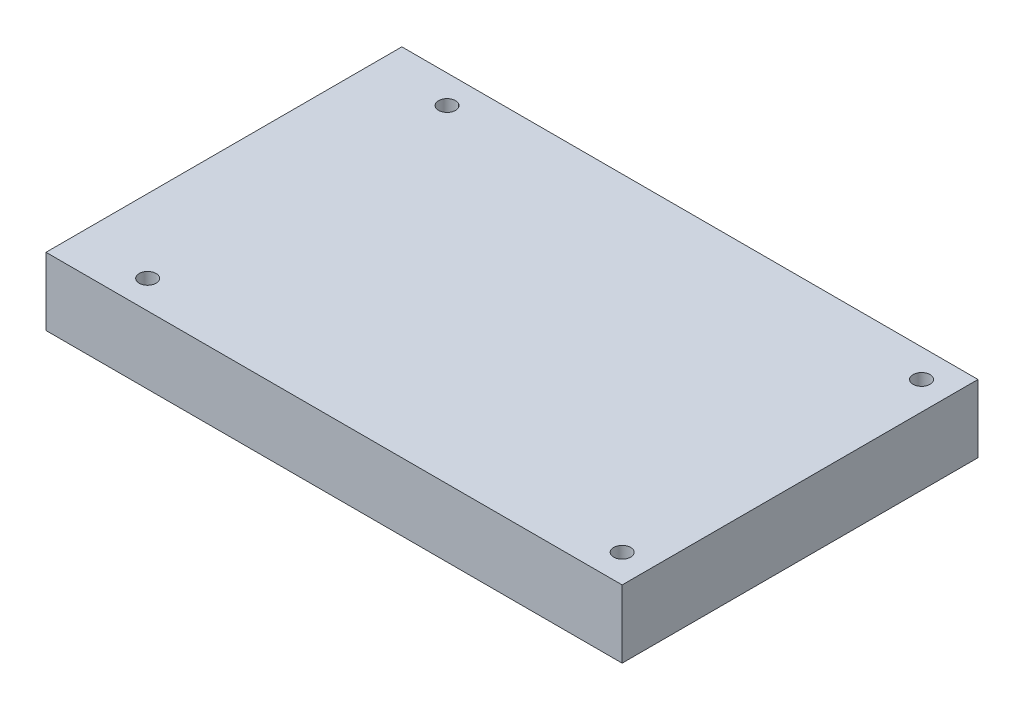
SolidWorks part; units mm, degrees
ref_plane "Front Plane" through (0, 0, 0) normal (0, 0, 1) x (1, 0, 0)
ref_plane "Top Plane" through (0, 0, 0) normal (0, 1, 0) x (1, 0, 0)
ref_plane "Right Plane" through (0, 0, 0) normal (1, 0, 0) x (0, 0, -1)
sketch "Sketch1" plane through (0, 0, 0) normal (0, 1, 0) x (1, 0, 0)
  line L1 (51, -31.5) -> (-51, -31.5)
  line L2 (51, -31.5) -> (51, 31.5)
  line L3 (51, 31.5) -> (-51, 31.5)
  line L4 (-51, -31.5) -> (-51, 31.5)
  line L5 (51, -31.5) -> (-51, 31.5) construction
  line L6 (51, 31.5) -> (-51, -31.5) construction
  point P0 (0, 0)
  dimension "D1" = 102
  dimension "D2" = 63
extrude "Boss-Extrude1" add sketch "Sketch1" along normal blind 12
sketch "Sketch2" plane through (0, 12, 0) normal (0, 1, 0) x (1, 0, 0)
  line L0 (-51, 31.5) -> (-51, -31.5) construction
  line L1 (51, 31.5) -> (-51, 31.5) construction
  circle A0 centre (-38, 26.5) radius 1.5
  circle A1 centre (46, 26.5) radius 1.5
  circle A2 centre (46, -26.5) radius 1.5
  circle A3 centre (-38, -26.5) radius 1.5
  dimension "D1" = 3
  dimension "D2" = 13
  dimension "D3" = 5
  dimension "D4" = 2
  dimension "D5" = 2
extrude "Cut-Extrude1" cut sketch "Sketch2" against normal through all
